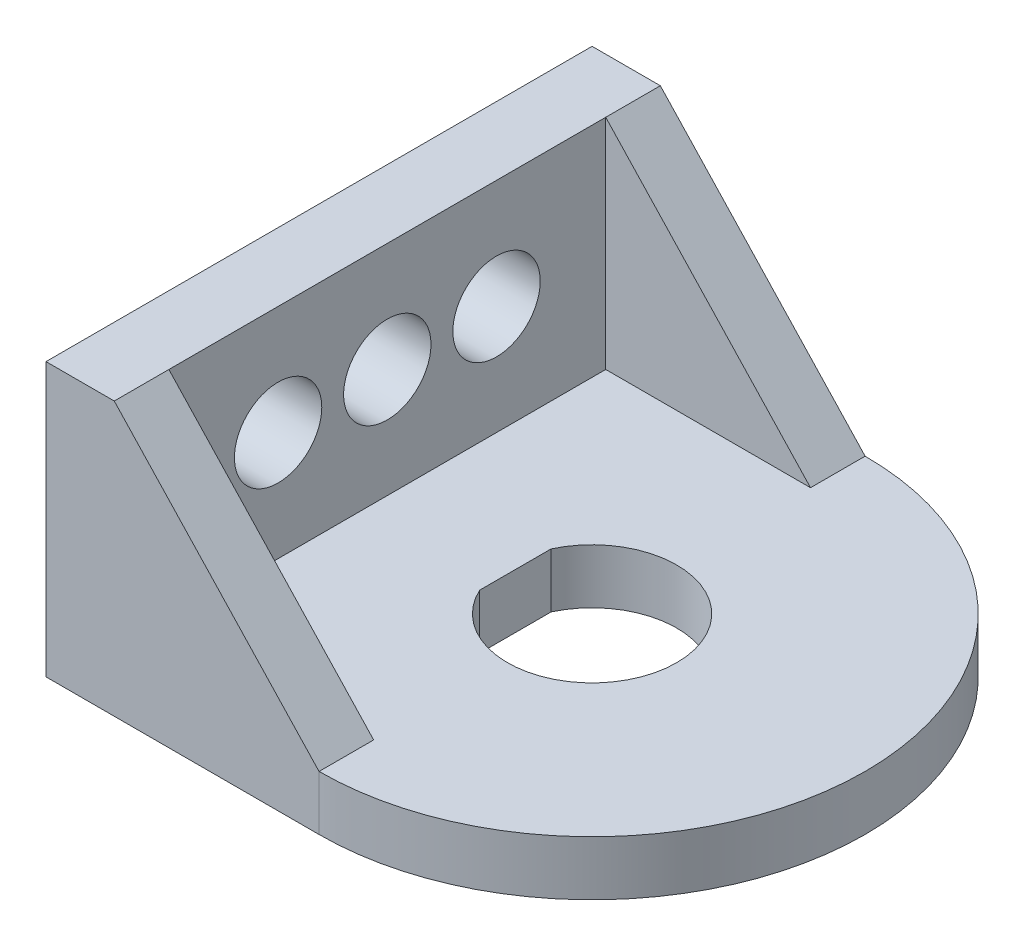
SolidWorks part; units mm, degrees
ref_plane "Front Plane" through (0, 0, 0) normal (0, 0, 1) x (1, 0, 0)
ref_plane "Top Plane" through (0, 0, 0) normal (0, 1, 0) x (1, 0, 0)
ref_plane "Right Plane" through (0, 0, 0) normal (1, 0, 0) x (0, 0, -1)
sketch "Sketch1" plane through (0, 0, 0) normal (0, 1, 0) x (1, 0, 0)
  line L0 (0, 0) -> (0, 10)
  line L1 (0, 10) -> (-10, 10)
  line L2 (-10, 10) -> (-10, 0)
  line L3 (-10, 0) -> (-10, -10)
  line L4 (-10, -10) -> (0, -10)
  line L5 (-10, 10) -> (-7.5, 10)
  line L6 (-7.5, 10) -> (-7.5, -10)
  circle A0 centre (0, 0) radius 3.1
  circle A1 centre (0, 0) radius 10
extrude "Boss-Extrude1" add sketch "Sketch1" along normal blind 2 contours A1 L6 A0 | A1 L3 L4 L6 | A1 L6 L4 | L6 A1 | A1 L6 L1 L2 | A1 L1 L6 region at (6.8832, 0, -6.8832) region at (-5.6944, 0, -9.0225) region at (-8.9477, 0, -7.05) region at (-8.5116, 0, 0) region at (-5.6944, 0, 9.0225) region at (-8.9477, 0, 7.05)
extrude "Boss-Extrude2" add sketch "Sketch1<3>" along normal blind 10 contours L6 A1 | A1 L6 L1 L2 | A1 L3 L4 L6 region at (-8.9477, 0, -7.05) region at (-8.5116, 0, 0) region at (-8.9477, 0, 7.05)
sketch "Sketch1<3>" plane through (0, 0, 0) normal (0, 1, 0) x (1, 0, 0) same geometry as "Sketch1"
sketch "Sketch2" plane through (0, 0, 10) normal (0, 0, 1) x (1, 0, 0)
  line L0 (-7.5, 10) -> (0, 2)
  line L1 (0, 2) -> (-7.5, 2)
  line L2 (-7.5, 2) -> (-7.5, 10)
extrude "Boss-Extrude3" add sketch "Sketch2" against normal blind 2
sketch "Sketch3" plane through (0, 0, -10) normal (0, 0, -1) x (-1, 0, 0)
  line L0 (0, 2) -> (7.5, 10)
  line L1 (3.1, 2) -> (-3.1, 2) construction
  line L2 (7.5, 10) -> (7.5, 2)
  line L3 (7.5, 2) -> (0, 2)
extrude "Boss-Extrude4" add sketch "Sketch3" against normal blind 2
sketch "Sketch4" plane through (-7.5, 0, 0) normal (1, 0, 0) x (0, 0, -1)
  line L1 (-8, 10) -> (-8, 2) construction
  line L2 (8, 10) -> (8, 2) construction
  line L3 (-8, 6) -> (0, 6)
  line L4 (0, 6) -> (8, 6)
  circle A0 centre (0, 6) radius 1.6
  circle A1 centre (-4, 6) radius 1.6
  circle A2 centre (4, 6) radius 1.6
extrude "Cut-Extrude1" cut sketch "Sketch4" against normal blind 5 contours L3 A1 | L4 A0 L3 | L4 A2 | L3 A0 L4 | L3 A1 | L4 A2 region at (-7.5, 6.6791, 4) region at (-7.5, 6.6791, -4) region at (-7.5, 5.3209, -4) region at (-7.5, 6.6791, 0) region at (-7.5, 5.3209, 0) region at (-7.5, 5.3209, 4)
sketch "Sketch5" plane through (0, 2, 0) normal (0, 1, 0) x (1, 0, 0)
  line L0 (3.1, 0) -> (-2.81, 0)
  line L1 (-2.81, 0) -> (-2.81, -1.3092)
  line L2 (-2.81, 0) -> (-2.81, 1.3092)
  circle A0 centre (0, 0) radius 3.1 construction
  arc A1 (-2.81, -1.3092) -> (-2.81, 1.3092) centre (0, 0) cw
  circle M11 centre (0, 0) radius 3.1
extrude "Boss-Extrude5" add sketch "Sketch5" against normal up to surface (2 mm away) contours L1 L2 M11 region at (-2.9265, 2, 0) up to face at (-2.5, 0, 0)
